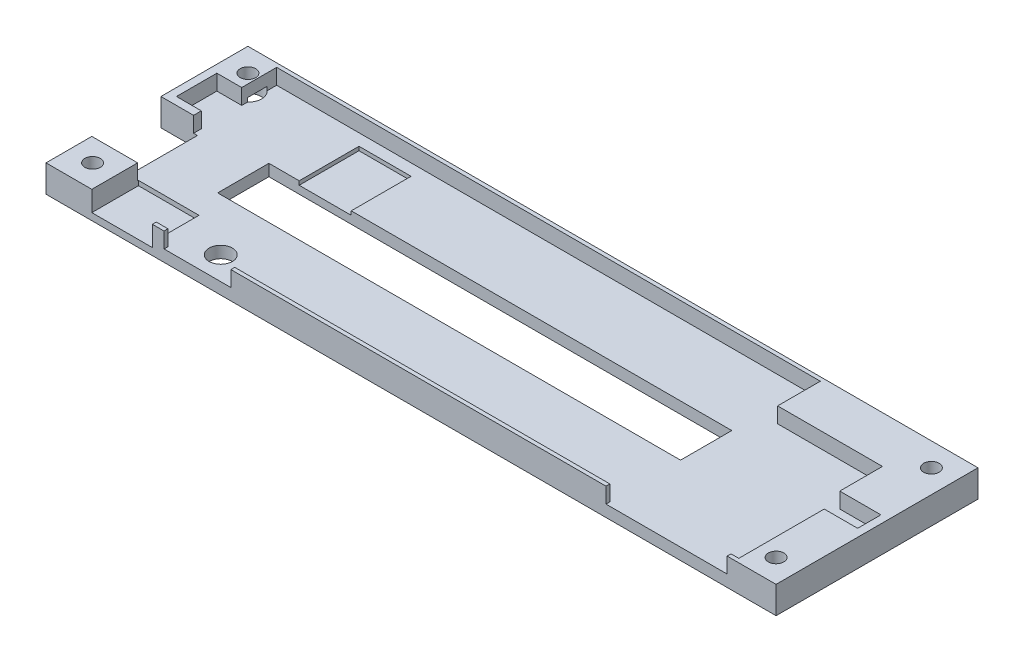
SolidWorks part; units mm, degrees
ref_plane "前视基准面" through (0, 0, 0) normal (0, 0, 1) x (1, 0, 0)
ref_plane "上视基准面" through (0, 0, 0) normal (0, 1, 0) x (1, 0, 0)
ref_plane "右视基准面" through (0, 0, 0) normal (1, 0, 0) x (0, 0, -1)
other "Configuration Table"
sketch "草图1" plane through (0, 0, 0) normal (0, 1, 0) x (1, 0, 0)
  line L1 (-47, -13) -> (47, -13)
  line L2 (-47, -13) -> (-47, 13)
  line L3 (-47, 13) -> (47, 13)
  line L4 (47, -13) -> (47, 13)
  line L5 (-47, -13) -> (47, 13) construction
  line L6 (-47, 13) -> (47, -13) construction
  circle A1 centre (-44, 10) radius 1
  circle A2 centre (-44, -10) radius 1
  circle A3 centre (44, 10) radius 1
  circle A4 centre (44, -10) radius 1
  point P0 (0, 0)
  dimension "D3" = 3
  dimension "D4" = 3
  dimension "D1" = 94
  dimension "D2" = 26
  dimension "D7" = 2
  dimension "D5" = 3
  dimension "D6" = 3
extrude "凸台-拉伸1" add sketch "草图1" along normal blind 3.5
sketch "草图2" plane through (0, 0, 0) normal (0, -1, 0) x (1, 0, 0)
  line L0 (-47, -13) -> (-47, 13) construction
  line L1 (-47, 7.1) -> (-42.3, 7.1)
  line L2 (-47, 7.1) -> (-47, -1.8)
  line L3 (-47, -1.8) -> (-42.3, -1.8)
  line L4 (-42.3, 7.1) -> (-42.3, -1.8)
  line L5 (-47, 13) -> (47, 13) construction
  line L6 (47, -13) -> (-47, -13) construction
  line L7 (-34.6, 0) -> (0, 0) construction
  line L8 (-34.6, 3.3) -> (25, 3.3)
  line L9 (-34.6, 3.3) -> (-34.6, -3.3)
  line L10 (-34.6, -3.3) -> (25, -3.3)
  line L11 (25, 3.3) -> (25, -3.3)
  line L12 (47, 13) -> (47, -13) construction
  dimension "D1" = 5.9
  dimension "D2" = 11.2
  dimension "D3" = 4.7
  dimension "D4" = 22
  dimension "D5" = 12.4
  dimension "D6" = 6.6
extrude "切除-拉伸1" cut sketch "草图2" against normal through all
sketch "草图3" plane through (0, 0, 0) normal (0, -1, 0) x (-1, 0, 0)
  line L0 (47, -13) -> (-47, -13) construction
  line L1 (31.8, -13) -> (23.2, -13)
  line L2 (31.8, -13) -> (31.8, -7)
  line L3 (31.8, -7) -> (23.2, -7)
  line L4 (23.2, -13) -> (23.2, -7)
  line L5 (47, -7.1) -> (47, -13) construction
  line L6 (-47, -13) -> (-47, 13) construction
  line L7 (31.8, -13) -> (23.2, -7) construction
  circle A0 centre (27.5, -10) radius 1.5
  dimension "D4" = 3
  dimension "D1" = 15.2
  dimension "D2" = 70.2
  dimension "D3" = 6
extrude "切除-拉伸2" cut sketch "草图3" against normal through all contours A0
sketch "草图4" plane through (0, 0, 0) normal (0, -1, 0) x (1, 0, 0)
  circle A0 centre (-44, 10) radius 1.75
  circle A1 centre (-44, -10) radius 1.75
  circle A2 centre (44, 10) radius 1.75
  circle A3 centre (44, -10) radius 1.75
  circle A4 centre (-44, 10) radius 1 construction
  circle A5 centre (-44, -10) radius 1 construction
  circle A6 centre (44, -10) radius 1 construction
  circle A7 centre (44, 10) radius 1 construction
  dimension "D1" = 3.5
extrude "切除-拉伸3" cut sketch "草图4" against normal offset from surface (2 mm away) 1.5 up to face at (-27.5, 3.5, 8.5)
sketch "草图5" plane through (0, 0, 13) normal (0, 0, 1) x (1, 0, 0)
  line L0 (-47, 3.5) -> (47, 3.5) construction
  line L1 (-41.1, 3.5) -> (-33.3, 3.5)
  line L2 (-41.1, 3.5) -> (-41.1, 0.9)
  line L3 (-41.1, 0.9) -> (-33.3, 0.9)
  line L4 (-33.3, 3.5) -> (-33.3, 0.9)
  line L5 (47, 3.5) -> (47, 0) construction
  line L6 (-31.8, 3.5) -> (-23.2, 3.5)
  line L7 (-31.8, 3.5) -> (-31.8, 1.5)
  line L8 (-31.8, 1.5) -> (-23.2, 1.5)
  line L9 (-23.2, 3.5) -> (-23.2, 1.5)
  line L10 (25.1, 3.5) -> (40.7, 3.5)
  line L11 (25.1, 3.5) -> (25.1, 1.5)
  line L12 (25.1, 1.5) -> (40.7, 1.5)
  line L13 (40.7, 3.5) -> (40.7, 1.5)
  line L14 (-47, 3.5) -> (-47, 0) construction
  dimension "D1" = 2
  dimension "D2" = 6.3
  dimension "D3" = 72.1
  dimension "D4" = 2.6
  dimension "D5" = 2
  dimension "D6" = 5.9
  dimension "D7" = 80.3
  dimension "D8" = 15.2
  dimension "D9" = 70.2
extrude "切除-拉伸4" cut sketch "草图5" against normal blind 6 contours L2 L3 L4 L1 | L8 L9 L6 L7
extrude "切除-拉伸5" cut sketch "草图5<3>" against normal blind 20 contours L13 L12 L11 L10
sketch "草图5<3>" plane through (0, 0, 13) normal (0, 0, 1) x (1, 0, 0) same geometry as "草图5"
sketch "草图6" plane through (0, 3.5, 0) normal (0, 1, 0) x (1, 0, 0)
  line L0 (47, 13) -> (-47, 13) construction
  line L1 (-42.8, 12.5) -> (27.2, 12.5)
  line L2 (-42.8, 12.5) -> (-42.8, -7.1)
  line L3 (-42.8, -7.1) -> (27.2, -7.1)
  line L4 (27.2, 12.5) -> (27.2, -7.1)
  line L5 (27.2, 1.5) -> (46, 1.5)
  line L6 (27.2, 1.5) -> (27.2, -1.5)
  line L7 (27.2, -1.5) -> (46, -1.5)
  line L8 (46, 1.5) -> (46, -1.5)
  line L9 (-23.2, -13) -> (25.1, -13) construction
  line L10 (41.7, -1.5) -> (-41.1, -1.5)
  line L11 (41.7, -1.5) -> (41.7, -12.5)
  line L12 (41.7, -12.5) -> (-41.1, -12.5)
  line L13 (-41.1, -1.5) -> (-41.1, -12.5)
  line L14 (0, 0) -> (46, 0) construction
  line L15 (-47, 13) -> (-47, 1.8) construction
  line L16 (-42.8, 8) -> (-46, 8)
  line L17 (-42.8, 8) -> (-42.8, 2.8)
  line L18 (-42.8, 2.8) -> (-46, 2.8)
  line L19 (-46, 8) -> (-46, 2.8)
  line L20 (-47, 1.8) -> (-42.3, 1.8) construction
  line L22 (-41.1, -7) -> (-41.1, -13) construction
  line L23 (-42.3, -7.1) -> (-47, -7.1) construction
  line L25 (47, -13) -> (47, 13) construction
  line L26 (40.7, 7) -> (40.7, -13) construction
  dimension "D1" = 0.5
  dimension "D2" = 0.5
  dimension "D3" = 3
  dimension "D4" = 1
  dimension "D5" = 5
  dimension "D6" = 4.2
  dimension "D7" = 1
  dimension "D8" = 1
  dimension "D9" = 1
  dimension "D10" = 70
extrude "切除-拉伸12" cut sketch "草图6" against normal blind 2 contours L16 L19 L18 L17 | L10 L13 L12 L11 | L5 L8 L7 L6 | L1 L4 L3 L2
sketch "草图7" plane through (0, 1.5, 0) normal (0, 1, 0) x (1, 0, 0)
  line L0 (25, 3.3) -> (-34.6, 3.3) construction
  line L1 (-30.7, 3.3) -> (-24, 3.3)
  line L2 (-30.7, 3.3) -> (-30.7, 11)
  line L3 (-30.7, 11) -> (-24, 11)
  line L4 (-24, 3.3) -> (-24, 11)
  line L5 (-47, 13) -> (-47, 1.8) construction
  line L6 (47, -13) -> (47, 13) construction
  line L7 (47, 13) -> (-47, 13) construction
  dimension "D1" = 16.3
  dimension "D2" = 71
  dimension "D3" = 2
extrude "切除-拉伸13" cut sketch "草图7" against normal blind 0.5
